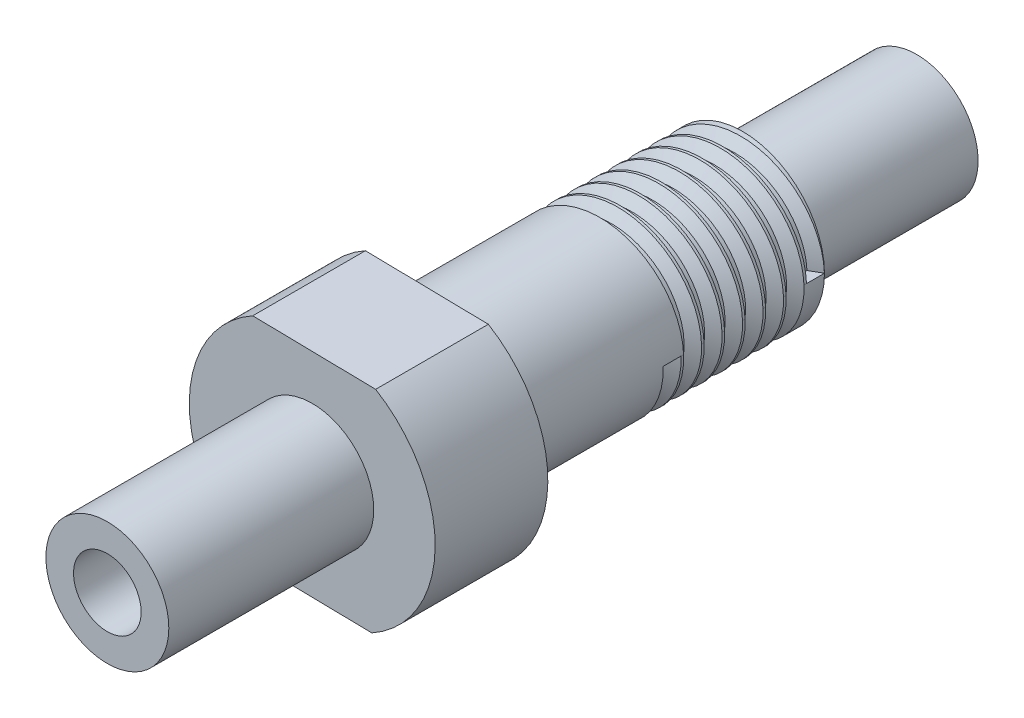
SolidWorks part; units mm, degrees
material "Stainless Steel (ferritic)"
ref_plane "Front Plane" through (0, 0, 0) normal (0, 0, 1) x (1, 0, 0)
ref_plane "Top Plane" through (0, 0, 0) normal (0, 1, 0) x (1, 0, 0)
ref_plane "Right Plane" through (0, 0, 0) normal (1, 0, 0) x (0, 0, -1)
sketch "Sketch1" plane through (0, 0, 0) normal (0, 0, 1) x (1, 0, 0)
  circle A0 centre (0, 0) radius 4
  dimension "D1" = 8
extrude "Boss-Extrude1" add sketch "Sketch1" along normal blind 16
sketch "Sketch2" plane through (0, 0, 16) normal (0, 0, 1) x (1, 0, 0)
  circle A0 centre (0, 0) radius 6
  dimension "D1" = 12
extrude "Boss-Extrude2" add sketch "Sketch2" along normal blind 8
sketch "Sketch3" plane through (0, 0, 0) normal (0, 0, -1) x (-1, 0, 0)
  circle A0 centre (0, 0) radius 3
  dimension "D1" = 6
extrude "Boss-Extrude3" add sketch "Sketch3" along normal blind 9
sketch "Sketch8" plane through (0, 0, 24) normal (0, 0, 1) x (1, 0, 0)
  circle A0 centre (0, 0) radius 3
  dimension "D1" = 6
extrude "Boss-Extrude4" add sketch "Sketch8" along normal blind 9
hole_wizard "M4x0.7 Tapped Hole2" positions "Sketch12" profile "Sketch13" tap size "M4x0.7" standard "ANSI Metric"
sketch "Sketch12" plane through (0, 0, 33) normal (0, 0, 1) x (1, 0, 0)
  point P0 (0, 0)
sketch "Sketch13" plane through (0, 0, 33) normal (1, 0, 0) x (0, -1, 0)
  line L0 (0, 0) -> (0, 12.9914)
  line L1 (0, 12.9914) -> (1.65, 12)
  line L2 (1.65, 12) -> (1.65, 0)
  line L5 (1.65, 0) -> (0, 0)
  line L10 (0, 12.9914) -> (-1.65, 12) construction
  line L11 (0, -6.35) -> (0, 107.95) construction
  dimension "Tap Drill Dia." = 3.3
  dimension "Tap Drill Depth" = 12
  dimension "Drill Angle" = 118
cosmetic thread "Hole Thread2" parameters "D1"=5, "D2"=4
hole_wizard "M4x0.7 Tapped Hole3" positions "Sketch32" profile "Sketch33" tap size "M4x0.7" standard "ANSI Metric"
sketch "Sketch32" plane through (0, 0, -9) normal (0, 0, -1) x (-1, 0, 0)
  point P0 (0, 0)
cosmetic thread "Hole Thread3" parameters "D1"=42, "D2"=4
sketch "Sketch33" plane through (0, 0, -9) normal (1, 0, 0) x (0, 1, 0)
  line L0 (0, 0) -> (0, 10.9914)
  line L1 (0, 10.9914) -> (1.65, 10)
  line L2 (1.65, 10) -> (1.65, 0)
  line L5 (1.65, 0) -> (0, 0)
  line L10 (0, 10.9914) -> (-1.65, 10) construction
  line L11 (0, -6.35) -> (0, 107.95) construction
  dimension "Tap Drill Dia." = 3.3
  dimension "Tap Drill Depth" = 10
  dimension "Drill Angle" = 118
sketch "Sketch36" plane through (0, 0, 24) normal (0, 0, 1) x (1, 0, 0)
  line L1 (3.0947, 5.1403) -> (-2.9043, 5.2502)
  line L2 (-2.9043, 5.2502) -> (-5.999, 0.1099)
  line L3 (-5.999, 0.1099) -> (-3.0947, -5.1403)
  line L4 (-3.0947, -5.1403) -> (2.9043, -5.2502)
  line L5 (2.9043, -5.2502) -> (5.999, -0.1099)
  line L6 (5.999, -0.1099) -> (3.0947, 5.1403)
  circle A0 centre (0, 0) radius 5.1962 construction
  circle A1 centre (0, 0) radius 6
  circle M2 centre (0, 0) radius 6
extrude "Cut-Extrude1" cut sketch "Sketch36" against normal blind 10 contours L1 M2 | L4 M2 region at (0.1011, 5.5187, 24) region at (-0.1011, -5.5187, 24)
sketch "Sketch37" plane through (0, 0, 24) normal (0, 0, 1) x (1, 0, 0)
  circle A0 centre (0, 0) radius 3
  circle A1 centre (0, 0) radius 7.7763
extrude "Cut-Extrude2" cut sketch "Sketch37" against normal blind 2.5
sketch "Sketch38" plane through (0, 0, 33) normal (0, 0, 1) x (1, 0, 0)
  circle A0 centre (0, 0) radius 1.65
  circle A1 centre (0, 0) radius 3.7442
extrude "Cut-Extrude3" cut sketch "Sketch38" against normal blind 2.5
sketch "Sketch39" plane through (0, 0, -9) normal (0, 0, -1) x (-1, 0, 0)
  circle A0 centre (0, 0) radius 1.65
  circle A1 centre (0, 0) radius 5.8234
extrude "Cut-Extrude4" cut sketch "Sketch39" against normal blind 2
sketch "Sketch40" plane through (0, 0, -7) normal (0, 0, -1) x (-1, 0, 0)
  circle A0 centre (0, 0) radius 3
  circle A1 centre (0, 0) radius 4.9187
extrude "Cut-Extrude5" cut sketch "Sketch40" against normal blind 7.5
sketch "Sketch42" plane through (0, 0, 0.5) normal (0, 0, -1) x (-1, 0, 0)
  circle A0 centre (0, 0) radius 3
  circle A1 centre (0, 0) radius 4
extrude "Boss-Extrude5" add sketch "Sketch42" against normal blind 7.5
thread "Thread1" pitch 1 method cut profile "Thread Profile5" start angle 0, offset 0, length 7, pitch 1, diameter 8
ref_plane "Plane5" through (4, 0, 0.5) normal (0, -1, 0) x (1, 0, 0)
sketch "Thread Profile5" plane through (4, 0, 0.5) normal (0, -1, 0) x (1, 0, 0)
  line L0 (0, 0) -> (0, 1) construction
  line L11 (0, 0) -> (0, 0.875)
  line L12 (0, 0.875) -> (-0.5413, 0.5625)
  line L13 (-0.5413, 0.5625) -> (-0.5413, 0.3125)
  line L15 (-0.5413, 0.3125) -> (0, 0)
  line L17 (-0.5413, 0.4375) -> (0, 0.4375) construction
  point P2 (0, 0)
  dimension "Pitch" = 1
  dimension "Profile_Angle" = 60
  dimension "Profile_Land" = 0.25
  dimension "Profile_Height" = 0.5413
sketch "Sketch55" plane through (0, 0, -7) normal (0, 0, -1) x (-1, 0, 0)
  circle A0 centre (0, 0) radius 1.65
  circle A1 centre (0, 0) radius 3
extrude "Boss-Extrude6" add sketch "Sketch55" along normal blind 1
sketch "Sketch56" plane through (0, 0, 30.5) normal (0, 0, 1) x (1, 0, 0)
  circle A0 centre (0, 0) radius 1.65
  circle A1 centre (0, 0) radius 3
extrude "Boss-Extrude7" add sketch "Sketch56" along normal blind 1
